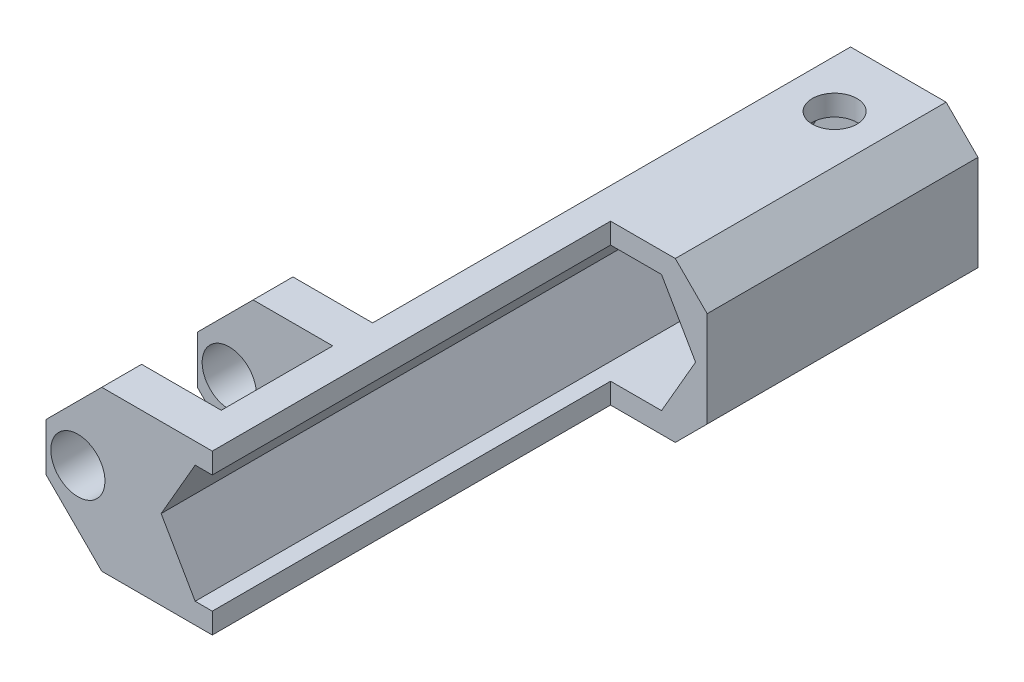
SolidWorks part; units mm, degrees
ref_plane "Plan de face" through (0, 0, 0) normal (0, 0, 1) x (1, 0, 0)
ref_plane "Plan de dessus" through (0, 0, 0) normal (0, 1, 0) x (1, 0, 0)
ref_plane "Plan de droite" through (0, 0, 0) normal (1, 0, 0) x (0, 0, -1)
sketch "Esquisse1" plane through (0, 0, 0) normal (0, 0, 1) x (1, 0, 0)
  line L1 (5, -5) -> (-5, -5)
  line L2 (5, -5) -> (5, 5)
  line L3 (5, 5) -> (-5, 5)
  line L4 (-5, -5) -> (-5, 5)
  line L5 (5, -5) -> (-5, 5) construction
  line L6 (5, 5) -> (-5, -5) construction
  point P0 (0, 0)
  dimension "D1" = 10
  dimension "D2" = 10
extrude "Boss.-Extru.1" add sketch "Esquisse1" along normal blind 42
sketch "Esquisse2" plane through (0, 0, 42) normal (0, 0, 1) x (1, 0, 0)
  line L1 (-4.2724, 0) -> (-2.1362, -3.7)
  line L2 (-2.1362, -3.7) -> (2.1362, -3.7)
  line L3 (2.1362, -3.7) -> (4.2724, 0)
  line L4 (4.2724, 0) -> (2.1362, 3.7)
  line L5 (2.1362, 3.7) -> (-2.1362, 3.7)
  line L6 (-2.1362, 3.7) -> (-4.2724, 0)
  circle A0 centre (0, 0) radius 3.7 construction
  dimension "D1" = 7.4
extrude "Enlèv. mat.-Extru.1" cut sketch "Esquisse2" against normal offset from surface (40 mm away) 2 up to face at (0, 0, 0)
sketch "Esquisse3" plane through (0, 0, 0) normal (0, 0, -1) x (-1, 0, 0)
  circle A0 centre (0, 0) radius 1.6
  dimension "D1" = 3.2
extrude "Enlèv. mat.-Extru.2" cut sketch "Esquisse3" against normal through all
sketch "Esquisse4" plane through (-5, 0, 0) normal (-1, 0, 0) x (0, 0, 1)
  line L0 (42, -5) -> (0, -5) construction
  line L1 (42, 5) -> (39.5, 5)
  line L2 (42, 5) -> (42, -5)
  line L3 (42, -5) -> (39.5, -5)
  line L4 (39.5, 5) -> (39.5, -5)
  line L5 (42, 5) -> (0, 5) construction
  line L6 (32.5, 5) -> (30, 5)
  line L7 (32.5, 5) -> (32.5, -5)
  line L8 (32.5, -5) -> (30, -5)
  line L9 (30, 5) -> (30, -5)
  dimension "D1" = 2.5
  dimension "D2" = 2.5
  dimension "D3" = 7
extrude "Boss.-Extru.2" add sketch "Esquisse4" along normal blind 6.5
chamfer "Chanfrein2" distance 3.5 angle 45 4 edges at (-11.5, -5, 40.75) (-11.5, 5, 40.75) (-11.5, -5, 31.25) (-11.5, 5, 31.25)
sketch "Esquisse5" plane through (0, 0, 30) normal (0, 0, -1) x (-1, 0, 0)
  line L0 (11.5, 1.5) -> (11.5, -1.5) construction
  line L2 (55, 0) -> (-55, 0) construction
  circle A0 centre (9.5, 0) radius 1.7
  point P2 (11.5, 0)
  dimension "D3" = 3.4
  dimension "D1" = 2
  dimension "D2" = 0
extrude "Enlèv. mat.-Extru.3" cut sketch "Esquisse5" against normal through all
ref_plane "Plan1" through (0, 0, 36) normal (0, 0, -1) x (-1, 0, 0)
chamfer "Chanfrein3" distance 2 angle 45 6 edges at (5, -5, 21) (5, 5, 21)
sketch "Esquisse9" plane through (0, 5, 0) normal (0, 1, 0) x (1, 0, 0)
  line L0 (3, 0) -> (-3, 0) construction
  circle A0 centre (0, -4) radius 1.4
  point P2 (0, 0)
  dimension "D1" = 2.8
  dimension "D2" = 4
extrude "Enlèv. mat.-Extru.4" cut sketch "Esquisse9" against normal blind 10
sketch "Esquisse10" plane through (0, 0, 42) normal (0, 0, 1) x (1, 0, 0)
  line L1 (5, -8.6933) -> (-1.063, -8.6933)
  line L2 (5, -8.6933) -> (5, 10.627)
  line L3 (5, 10.627) -> (-1.063, 10.627)
  line L4 (-1.063, -8.6933) -> (-1.063, 10.627)
extrude "Enlèv. mat.-Extru.5" cut sketch "Esquisse10" against normal blind 25
equation "\"¨3.4\"=3.3"
